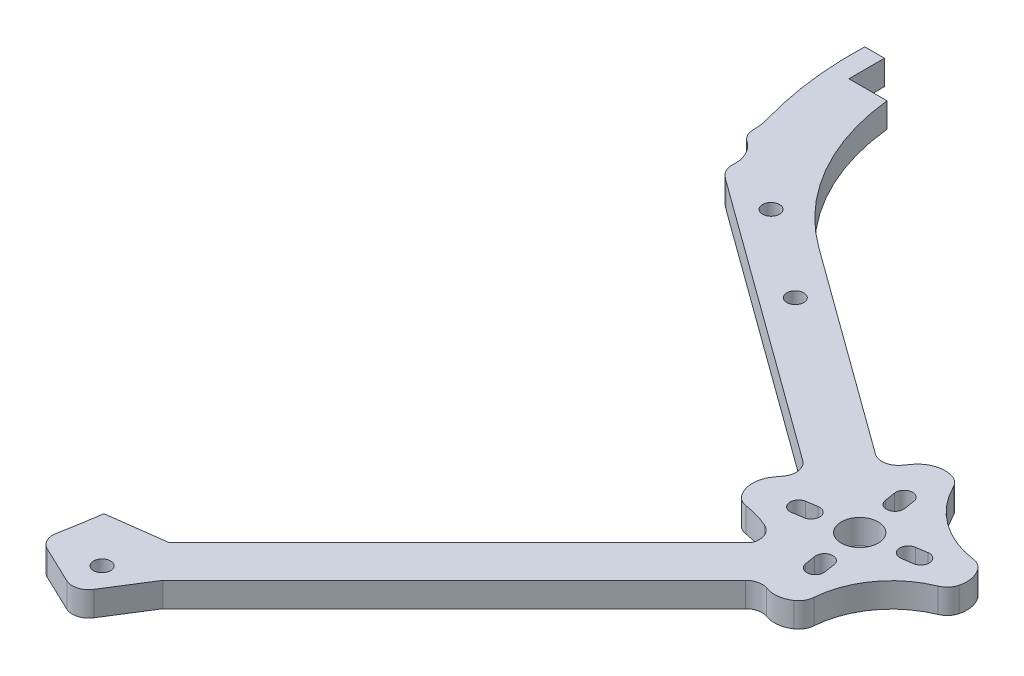
SolidWorks part; units mm, degrees
material "PPS"
ref_plane "前视基准面" through (0, 0, 0) normal (0, 0, 1) x (1, 0, 0)
ref_plane "上视基准面" through (0, 0, 0) normal (0, 1, 0) x (1, 0, 0)
ref_plane "右视基准面" through (0, 0, 0) normal (1, 0, 0) x (0, 0, -1)
sketch "草图3" plane through (0, 0, 0) normal (0, 1, 0) x (1, 0, 0)
  line L0 (0, 0) -> (35.4735, 0) construction
  line L1 (0, 0) -> (62.3757, -45.3186) construction
  line L2 (41.1319, -24.0128) -> (94.6944, -62.9282)
  line L3 (94.6944, -62.9282) -> (100.1314, -55.4448)
  line L4 (100.1314, -55.4448) -> (122.7839, -71.9028)
  line L5 (122.7839, -71.9028) -> (106.3259, -94.5552)
  line L6 (83.6734, -78.0972) -> (106.3259, -94.5552) construction
  line L9 (77.9994, -109.7251) -> (128.6275, -40.0415) construction
  line L11 (103.2286, -75) -> (90.242, -77.0569) construction
  line L13 (110.8832, -73.7876) -> (112.8586, -73.4748) construction
  line L14 (110.6408, -72.2567) -> (112.6161, -71.9438)
  line L15 (111.1257, -75.3185) -> (113.1011, -75.0057)
  line L16 (102.0163, -67.3454) -> (101.7034, -65.37) construction
  line L17 (103.5472, -67.1029) -> (103.2343, -65.1276)
  line L18 (100.4854, -67.5879) -> (100.1725, -65.6125)
  line L19 (95.5741, -76.2124) -> (93.5987, -76.5252) construction
  line L20 (95.8165, -77.7433) -> (93.8412, -78.0562)
  line L21 (95.3316, -74.6815) -> (93.3562, -74.9943)
  line L22 (104.441, -82.6546) -> (104.7539, -84.63) construction
  line L23 (102.9101, -82.8971) -> (103.223, -84.8724)
  line L24 (105.9719, -82.4121) -> (106.2848, -84.3875)
  line L36 (68.8077, -72) -> (90.242, -72) construction
  line L51 (41.6712, -139.6547) -> (94.9997, -86.3262)
  line L52 (94.9997, -86.3262) -> (83.6734, -78.0972)
  line L58 (47.1809, -146.1658) -> (101.962, -91.3847)
  line L61 (101.962, -91.3847) -> (106.3259, -94.5552)
  line L63 (31.6811, -151.7709) -> (40.8875, -156.1591)
  line L64 (47.1809, -146.1658) -> (40.8875, -156.1591)
  line L65 (41.6712, -139.6547) -> (31.2614, -141.0241)
  line L66 (42.309, -153.902) -> (47.6512, -145.4189) construction
  line L67 (31.6811, -151.7709) -> (38.4796, -155.0114) construction
  line L68 (89.1104, -70.6138) -> (83.6734, -78.0972)
  line L69 (35.5479, -31.6984) -> (89.1104, -70.6138)
  circle A5 centre (103.2286, -75) radius 3.375
  arc A6 (110.6408, -72.2567) -> (111.1257, -75.3185) centre (110.8832, -73.7876) ccw
  arc A7 (113.1011, -75.0057) -> (112.6161, -71.9438) centre (112.8586, -73.4748) ccw
  arc A8 (103.5472, -67.1029) -> (100.4854, -67.5879) centre (102.0163, -67.3454) cw
  arc A9 (100.1725, -65.6125) -> (103.2343, -65.1276) centre (101.7034, -65.37) cw
  arc A10 (95.8165, -77.7433) -> (95.3316, -74.6815) centre (95.5741, -76.2124) ccw
  arc A11 (93.3562, -74.9943) -> (93.8412, -78.0562) centre (93.5987, -76.5252) ccw
  arc A12 (102.9101, -82.8971) -> (105.9719, -82.4121) centre (104.441, -82.6546) cw
  arc A13 (106.2848, -84.3875) -> (103.223, -84.8724) centre (104.7539, -84.63) cw
  arc A16 (41.1319, -24.0128) -> (35.5479, -31.6984) centre (38.3399, -27.8556) ccw
  circle A17 centre (103.2286, -75) radius 66.25 construction
  circle A18 centre (44.0442, -32) radius 1.55
  circle A19 centre (60.2246, -43.7557) radius 1.55
  circle A28 centre (39.335, -149.4323) radius 1.55
  arc A29 (30.0249, -148.5011) -> (31.2329, -97.7907) centre (-122.0773, -119.5082) ccw construction
  arc A33 (31.2614, -141.0241) -> (30.0249, -148.5011) centre (-122.0773, -119.5082) cw
  arc A34 (30.0249, -148.5011) -> (31.6811, -151.7709) centre (32.9719, -149.0628) ccw construction
  arc A35 (30.0249, -148.5011) -> (31.6811, -151.7709) centre (32.9719, -149.0628) ccw
  point P11 (114.5549, -83.229)
  point P20 (111.8709, -73.6312)
  point P27 (101.8598, -66.3577)
  point P35 (94.5864, -76.3688)
  point P42 (104.5974, -83.6423)
  point P54 (94.9997, -86.3262)
  dimension "D2" = 45
  dimension "D3" = 6.75
  dimension "D4" = 1.55
  dimension "D7" = 14
  dimension "D11" = 132.5
  dimension "D12" = 3.1
  dimension "D26" = 8.5
  dimension "D27" = 3.1
  dimension "D1" = 36
  dimension "D5" = 2
  dimension "D6" = 7.75
  dimension "D8" = 14
  dimension "D9" = 4.75
  dimension "D10" = 75
  dimension "D13" = 32
  dimension "D14" = 20
  dimension "D22" = 72
  dimension "D25" = 45
extrude "凸台-拉伸1" add sketch "草图3" along normal blind 4.5 contours L5 L4 L3 L2 A16 L69 L52 L51 A19 A18 A11 L21 A10 L20 A7 L15 A6 L14 region at (66.9596, 0, 44.7829)
fillet "圆角-美观1" radius 5 4 edges at (100.1314, 2.25, 55.4448) (122.7839, 2.25, 71.9028) (106.3259, 2.25, 94.5552) (83.6734, 2.25, 78.0972)
sketch "草图4" plane through (0, 4.5, 0) normal (0, 1, 0) x (1, 0, 0)
  line L0 (104.1765, -58.3837) -> (118.7388, -68.9638)
  line L1 (119.8449, -75.9478) -> (109.2648, -90.5101)
  line L3 (103.2286, -75) -> (124.6569, -90.5685) construction
  line L4 (103.2286, -75) -> (89.033, -94.5387) construction
  line L5 (87.7185, -81.0362) -> (102.2808, -91.6163)
  line L6 (96.4624, -84.313) -> (94.9997, -86.3262)
  line L7 (41.1319, -24.0128) -> (94.6944, -62.9282) construction
  arc A2 (102.2808, -91.6163) -> (87.7185, -81.0362) centre (86.1651, -98.4859) ccw
  arc A8 (118.7388, -68.9638) -> (104.1765, -58.3837) centre (120.2922, -51.5141) cw
  arc A9 (119.8449, -75.9478) -> (109.2648, -90.5101) centre (124.6569, -90.5685) ccw
  line M97 (87.7185, -81.0362) -> (94.9997, -86.3262)
extrude "圆弧-美观2" cut sketch "草图4" against normal up to next contours A8 L0 | L1 A9 | L6 A2 M97 region at (110.8688, 4.5, 64.4842) region at (113.6066, 4.5, 82.54) region at (92.8302, 4.5, 83.5118)
fillet "圆角-美观3" radius 3 10 edges at (104.1765, 2.25, 58.3837) (118.7388, 2.25, 68.9638) (119.8449, 2.25, 75.9478) (94.6944, 2.25, 62.9282) (40.8875, 2.25, 156.1591) (109.2648, 2.25, 90.5101) (101.962, 2.25, 91.3847) (89.1104, 2.25, 70.6138) (87.7185, 2.25, 81.0362) (96.4624, 2.25, 84.313)
sketch "草图5" plane through (0, 0, 0) normal (0, 1, 0) x (1, 0, 0)
  line L0 (0, 0) -> (132.1913, 0) construction
  line L1 (0, 0) -> (0, 63.0505) construction
  line L2 (41.1319, -24.0128) -> (54.395, -33.649)
  line L3 (30.5, 2.25) -> (26.9026, 2.25)
  line L4 (30.5, 2.25) -> (30.5, -3.25)
  line L5 (30.5, -3.25) -> (30.5, -4.25)
  line L6 (30.5, -4.25) -> (37.4677, -4.25)
  line L7 (41.1319, -24.0128) -> (92.2673, -61.1648) construction
  line L8 (37.3772, -3.25) -> (30.5, -3.25) construction
  line L9 (30.5, -3.25) -> (30.5, 3.25) construction
  line L10 (30.5, 3.25) -> (26.9448, 3.25) construction
  line L11 (41.1319, -24.0128) -> (35.5479, -31.6984)
  line L13 (34.4971, -25.0636) -> (29.8517, -19.5014) construction
  arc A0 (34.4971, -25.0636) -> (41.1319, -24.0128) centre (38.3399, -27.8556) cw construction
  arc A1 (34.4971, -25.0636) -> (35.5479, -31.6984) centre (38.3399, -27.8556) ccw construction
  arc A2 (29.8211, -20.7007) -> (35.5479, -31.6984) centre (43.7171, -20.4546) ccw
  arc A3 (29.8211, -20.7007) -> (29.4289, -18.099) centre (19.8227, -20.8778) ccw
  arc A6 (26.9026, 2.25) -> (29.4289, -18.099) centre (91.9966, 0) ccw
  arc A7 (29.8202, 19.4008) -> (29.8202, -19.4008) centre (91.9966, 0) ccw construction
  arc A8 (54.395, -33.649) -> (37.3772, -3.25) centre (78.8424, 0) cw construction
  arc A9 (29.4289, -18.099) -> (26.9448, 3.25) centre (91.9966, 0) cw construction
  arc A12 (41.1319, -24.0128) -> (35.5479, -31.6984) centre (38.3399, -27.8556) ccw construction
  arc A14 (54.395, 33.649) -> (54.395, -33.649) centre (78.8424, 0) ccw construction
  arc A15 (37.4677, -4.25) -> (42.5499, -20.3171) centre (78.8424, 0) ccw
  arc A16 (54.395, -33.649) -> (42.5499, -20.3171) centre (78.8424, 0) cw
  dimension "D1" = 3.25
  dimension "D5" = 1
  dimension "D2" = 3.25
  dimension "D3" = 30.5
  dimension "D4" = 1
extrude "机臂配合防旋转" add sketch "草图5" along normal up to surface (4.5 mm away) up to face at (39.335, 4.5, 150.9823)
sketch "草图7" plane through (0, 0, 0) normal (0, 1, 0) x (1, 0, 0)
  circle A1 centre (44.0442, -32) radius 1.55 construction
  circle A6 centre (28, -28) radius 3.15 construction
  circle A7 centre (28, -28) radius 5.5
  dimension "D1" = 11
  dimension "D2" = 1.55
  dimension "D3" = 4
extrude "减震球让位" cut sketch "草图7" along normal through all
fillet "圆角1" radius 3 2 edges at (33.2595, 2.25, 29.6087) (30.034, 2.25, 22.8899)
